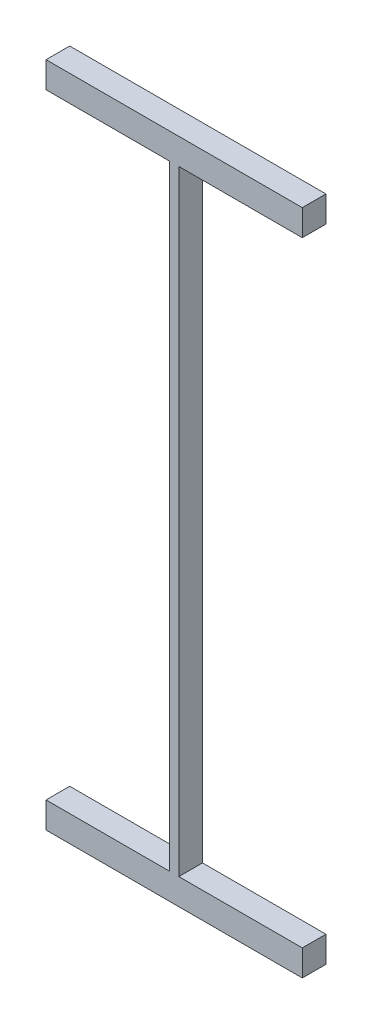
SolidWorks part; units mm, degrees
ref_plane "Front Plane" through (0, 0, 0) normal (0, 0, 1) x (1, 0, 0)
ref_plane "Top Plane" through (0, 0, 0) normal (0, 1, 0) x (1, 0, 0)
ref_plane "Right Plane" through (0, 0, 0) normal (1, 0, 0) x (0, 0, -1)
sketch "Sketch1" plane through (0, 0, 0) normal (0, 0, 1) x (1, 0, 0)
  line L0 (-137.5, -330) -> (-137.5, -358)
  line L1 (-137.5, 358) -> (137.5, 358)
  line L2 (-137.5, 358) -> (-137.5, 330)
  line L3 (-137.5, -358) -> (137.5, -358)
  line L4 (0, 358) -> (0, -358) construction
  line L5 (-137.5, 330) -> (-5, 330)
  line L6 (137.5, -330) -> (137.5, -358)
  line L7 (-137.5, -330) -> (-5, -330)
  line L8 (-5, 330) -> (-5, -330)
  line L9 (137.5, -330) -> (5, -330)
  line L10 (5, 330) -> (5, -330)
  line L11 (137.5, 330) -> (5, 330)
  line L12 (137.5, 358) -> (137.5, 330)
  dimension "Width" = 275
  dimension "Depth" = 716
  dimension "Web_thickness" = 10
  dimension "Thickness" = 28
extrude "BaseSection" add sketch "Sketch1" along normal mid plane 25.4
